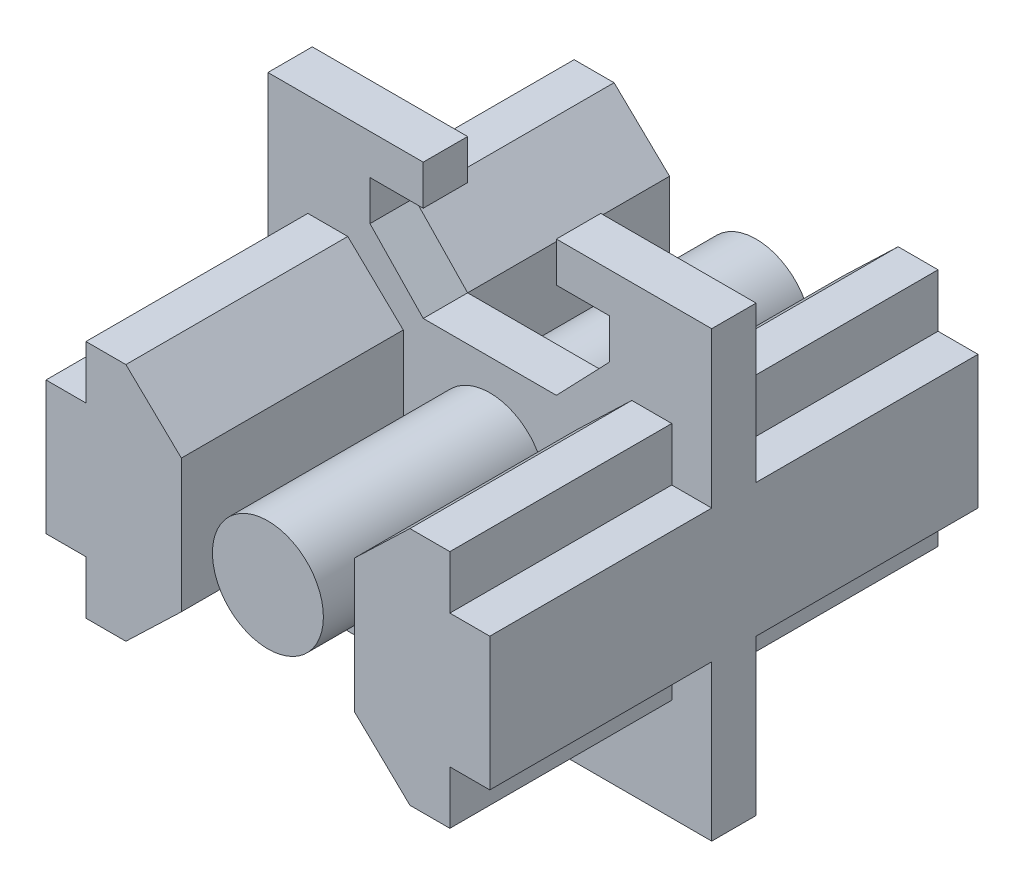
SolidWorks part; units mm, degrees
ref_plane "Front Plane" through (0, 0, 0) normal (0, 0, 1) x (1, 0, 0)
ref_plane "Top Plane" through (0, 0, 0) normal (0, 1, 0) x (1, 0, 0)
ref_plane "Right Plane" through (0, 0, 0) normal (1, 0, 0) x (0, 0, -1)
sketch "Sketch1" plane through (0, 0, 0) normal (0, 0, 1) x (1, 0, 0)
  line L0 (7, 0) -> (13, 0)
  line L1 (0, 0) -> (20, 0)
  line L2 (0, 0) -> (0, -20)
  line L3 (0, -20) -> (20, -20)
  line L4 (20, 0) -> (20, -20)
  line L5 (13, 0) -> (13, -1.8)
  line L6 (13, -1.8) -> (15.4, -1.8)
  line L7 (15.4, -1.8) -> (15.4, -3.6)
  line L8 (20, -13) -> (18.2, -13)
  line L9 (7, -6.1) -> (13, -6.1)
  line L10 (13, -6.1) -> (15.4, -3.6)
  line L18 (20, -6.6) -> (20, -12.6)
  line L46 (13.9, -6.6) -> (13.9, -12.6) [skipped]
  line L48 (20, -12.6) -> (18.2, -12.6) [skipped]
  line L49 (18.2, -12.6) -> (18.2, -15) [skipped]
  line L50 (18.2, -15) -> (16.4, -15) [skipped]
  line L51 (13.9, -12.6) -> (16.4, -15) [skipped]
  line L54 (13.4, -13.5) -> (7.4, -13.5) [skipped]
  line L55 (7.4, -17.8) -> (5, -17.8) [skipped]
  line L56 (5, -17.8) -> (5, -16) [skipped]
  line L57 (7.4, -13.5) -> (5, -16) [skipped]
  line L58 (7.4, -19.6) -> (7.4, -17.8) [skipped]
  line L61 (6.5, -13) -> (6.5, -7) [skipped]
  line L62 (6.5, -7) -> (4, -4.6) [skipped]
  line L63 (2.2, -4.6) -> (4, -4.6) [skipped]
  line L64 (2.2, -7) -> (2.2, -4.6) [skipped]
  line L65 (0.4, -7) -> (2.2, -7) [skipped]
  line L66 (7, -6.1) -> (4.6, -3.6)
  line L67 (4.6, -1.8) -> (4.6, -3.6)
  line L68 (7, -1.8) -> (4.6, -1.8)
  line L69 (7, 0) -> (7, -1.8)
  line L91 (18.2, -13) -> (18.2, -15.4)
  line L92 (18.2, -15.4) -> (16.4, -15.4)
  line L93 (13.9, -13) -> (16.4, -15.4)
  line L94 (13.9, -7) -> (13.9, -13)
  line L95 (13.9, -7) -> (16.4, -4.6)
  line L96 (18.2, -4.6) -> (16.4, -4.6)
  line L97 (18.2, -7) -> (18.2, -4.6)
  line L98 (20, -7) -> (18.2, -7)
  line L99 (20, -7) -> (20, -13)
  line L100 (13.4, -19.6) -> (7.4, -19.6) [skipped]
  line L101 (7, -20) -> (7, -18.2)
  line L102 (7, -18.2) -> (4.6, -18.2)
  line L103 (4.6, -18.2) -> (4.6, -16.4)
  line L104 (7, -13.9) -> (4.6, -16.4)
  line L105 (13, -13.9) -> (7, -13.9)
  line L106 (13, -13.9) -> (15.4, -16.4)
  line L107 (15.4, -18.2) -> (15.4, -16.4)
  line L108 (13, -18.2) -> (15.4, -18.2)
  line L109 (13, -20) -> (13, -18.2)
  line L110 (13, -20) -> (7, -20)
  line L111 (0, -7) -> (1.8, -7)
  line L112 (1.8, -7) -> (1.8, -4.6)
  line L113 (0.4, -13) -> (0.4, -7) [skipped]
  line L114 (1.8, -4.6) -> (3.6, -4.6)
  line L115 (6.1, -7) -> (3.6, -4.6)
  line L116 (6.1, -13) -> (6.1, -7)
  line L117 (6.1, -13) -> (3.6, -15.4)
  line L118 (1.8, -15.4) -> (3.6, -15.4)
  line L119 (1.8, -13) -> (1.8, -15.4)
  line L120 (0, -13) -> (1.8, -13)
  line L121 (0, -13) -> (0, -7)
  circle A1 centre (10, -10) radius 2.5
  point P8 (10, 0)
  point P18 (10, -6.1)
  point P54 (10, -10)
  dimension "D7" = 5
  dimension "D8" = 4
  dimension "D1" = 20
  dimension "D2" = 20
  dimension "D3" = 6
  dimension "D4" = 1.8
  dimension "D5" = 2.4
  dimension "D6" = 1.8
  dimension "D9" = 3.9
  dimension "D12" = 7
  dimension "D13" = 3.9
  dimension "D11" = 3.9
  dimension "D10" = 4
extrude "Boss-Extrude1" add sketch "Sketch1" along normal mid plane 22 contours L18 L98 L97 L96 L95 L94 L93 L92 L91 L8 L4 | L2 L120 L119 L118 L117 L116 L115 L114 L112 L111 | A1 region at (0.2, -10, 0) region at (3.3241, -10.0842, 0) region at (16.8419, -9.8, 0) region at (2, -5.8, 0) region at (19.1, -12.8, 0) region at (18.1487, -15.2, 0) region at (10, -10, 0)
extrude "Boss-Extrude2" add sketch "Sketch1<11>" along normal mid plane 2 contours L120 L2 L3 L101 L102 L103 L104 L105 L106 L107 L108 L109 L4 L8 L91 L92 L93 L94 L95 L96 L97 L98 L1 L5 L6 L7 L10 L9 L66 L67 L68 L69 L111 L112 L114 L115 L116 L117 L118 L119 A1 region at (6.7172, -0.9, 0)
sketch "Sketch1<11>" plane through (0, 0, 0) normal (0, 0, 1) x (1, 0, 0) same geometry as "Sketch1"
